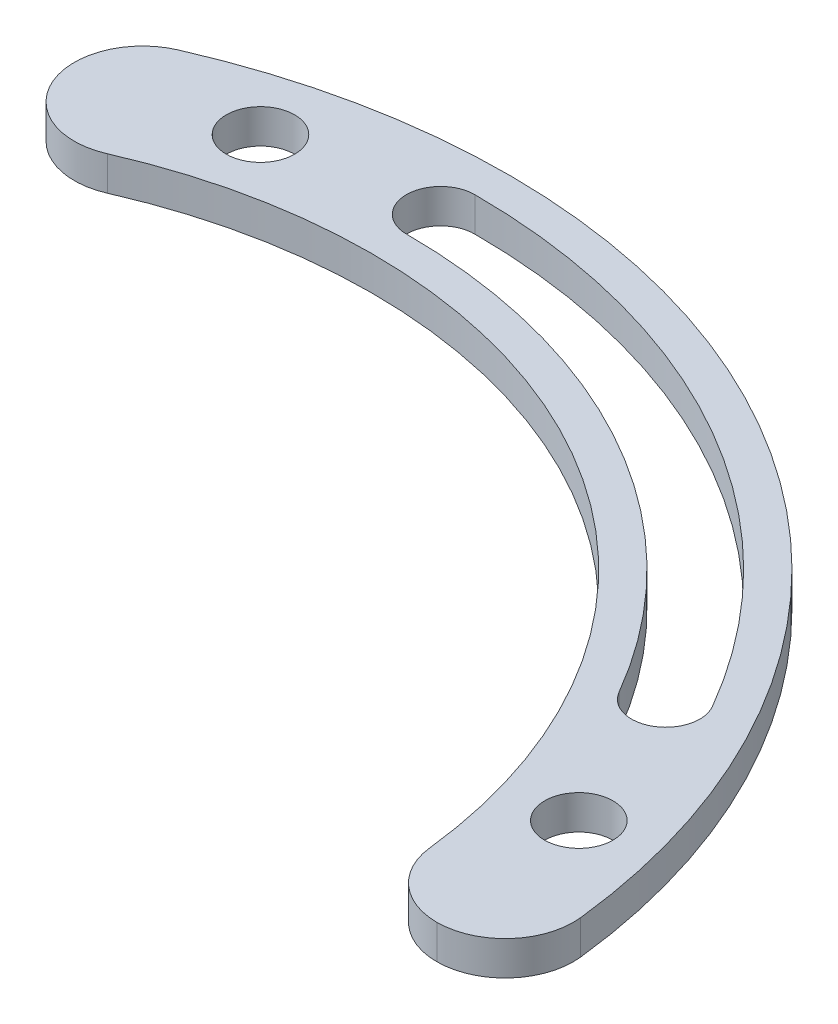
SolidWorks part; units mm, degrees
ref_plane "前视基准面" through (0, 0, 0) normal (0, 0, 1) x (1, 0, 0)
ref_plane "上视基准面" through (0, 0, 0) normal (0, 1, 0) x (1, 0, 0)
ref_plane "右视基准面" through (0, 0, 0) normal (1, 0, 0) x (0, 0, -1)
other "Configuration Table"
sketch "草图1" plane through (0, 0, 0) normal (0, 1, 0) x (1, 0, 0)
  line L0 (0, 0) -> (20, 0) construction
  line L1 (0, 0) -> (-10, 17.3205) construction
  line L2 (20, 0) -> (16, 0)
  line L3 (-10, 17.3205) -> (-8, 13.8564)
  line L4 (-4.6587, 17.3867) -> (0, 0) construction
  line L5 (0, 0) -> (17.3867, 4.6587) construction
  line L6 (0, 0) -> (10, 17.3205) construction
  line L7 (0, 18) -> (0, 0) construction
  line L8 (0, 0) -> (15.5885, 9) construction
  arc A0 (20, 0) -> (-10, 17.3205) centre (0, 0) ccw
  arc A1 (16, 0) -> (-8, 13.8564) centre (0, 0) ccw
  arc A2 (18, 0) -> (-9, 15.5885) centre (0, 0) ccw construction
  circle A3 centre (-4.6587, 17.3867) radius 1
  circle A4 centre (17.3867, 4.6587) radius 1
  arc A5 (0, 18) -> (15.5885, 9) centre (0, 0) cw construction
  arc A6 (16.4545, 9.5) -> (0, 19) centre (0, 0) ccw
  arc A7 (14.7224, 8.5) -> (0, 17) centre (0, 0) ccw
  arc A8 (14.7224, 8.5) -> (16.4545, 9.5) centre (15.5885, 9) ccw
  arc A9 (0, 19) -> (0, 17) centre (0, 18) ccw
  arc A10 (19, 0) -> (-9.5, 16.4545) centre (0, 0) ccw construction
  point P9 (-9, 15.5885)
  point P16 (9, 15.5885)
  dimension "D6" = 2
  dimension "D7" = 2
  dimension "D8" = 19
  dimension "D1" = 120
  dimension "D2" = 18
  dimension "D3" = 16
  dimension "D4" = 90
  dimension "D5" = 45
  dimension "D9" = 60
  dimension "D10" = 30
extrude "凸台-拉伸1" add sketch "草图1" along normal blind 1
fillet "圆角1" radius 2 4 edges at (-8, 0.5, -13.8564) (-10, 0.5, -17.3205) (16, 0.5, 0) (20, 0.5, 0)
